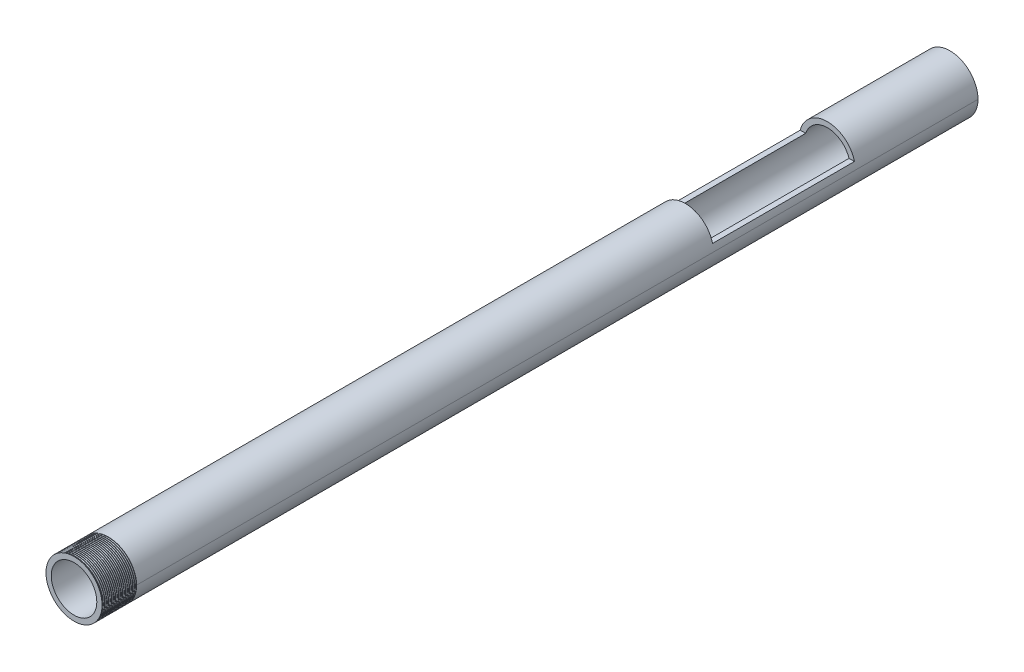
SolidWorks part; units mm, degrees
ref_plane "Front Plane" through (0, 0, 0) normal (0, 0, 1) x (1, 0, 0)
ref_plane "Top Plane" through (0, 0, 0) normal (0, 1, 0) x (1, 0, 0)
ref_plane "Right Plane" through (0, 0, 0) normal (1, 0, 0) x (0, 0, -1)
sketch "Sketch1" plane through (0, 0, 0) normal (0, 0, 1) x (1, 0, 0)
  circle A0 centre (0, 0) radius 13
  circle A1 centre (0, 0) radius 16
  point P3 (16, 0)
  point P5 (-16, 0)
  dimension "D1" = 26
  dimension "D2" = 32
extrude "Boss-Extrude1" add sketch "Sketch1" along normal blind 500
sketch "Sketch2" plane through (0, 0, 0) normal (1, 0, 0) x (0, 0, -1)
  line L1 (-70, 54) -> (-151, 54)
  line L2 (-70, 54) -> (-70, 4)
  line L3 (-70, 4) -> (-151, 4)
  line L4 (-151, 54) -> (-151, 4)
  dimension "D1" = 81
  dimension "D2" = 50
  dimension "D3" = 70
  dimension "D4" = 20
extrude "Cut-Extrude1" cut sketch "Sketch2" against normal blind 530 and the other way blind 530
thread "Thread1" pitch 0.25 method cut profile "Thread Profile1" start angle 0, offset 0, length 20, pitch 1, diameter 32
ref_plane "Plane1" through (-16, 0, 500) normal (0, -1, 0) x (-1, 0, 0)
sketch "Thread Profile1" plane through (-16, 0, 500) normal (0, -1, 0) x (-1, 0, 0)
  line L0 (0, 0) -> (0, 0.25) construction
  line L11 (0, 0) -> (0, 0.2187)
  line L12 (0, 0.2187) -> (-0.1353, 0.1406)
  line L13 (-0.1353, 0.1406) -> (-0.1353, 0.0781)
  line L15 (-0.1353, 0.0781) -> (0, 0)
  line L17 (-0.1353, 0.1094) -> (0, 0.1094) construction
  point P2 (0, 0)
  dimension "Pitch" = 0.25
  dimension "Profile_Angle" = 60
  dimension "Profile_Land" = 0.0625
  dimension "Profile_Height" = 0.1353
split line "Split Line1"
sketch "Sketch3" plane through (0, 0, 0) normal (0, 0, -1) x (-1, 0, 0)
  line L0 (-16, 0) -> (16, 0)
split line "Split Line2"
